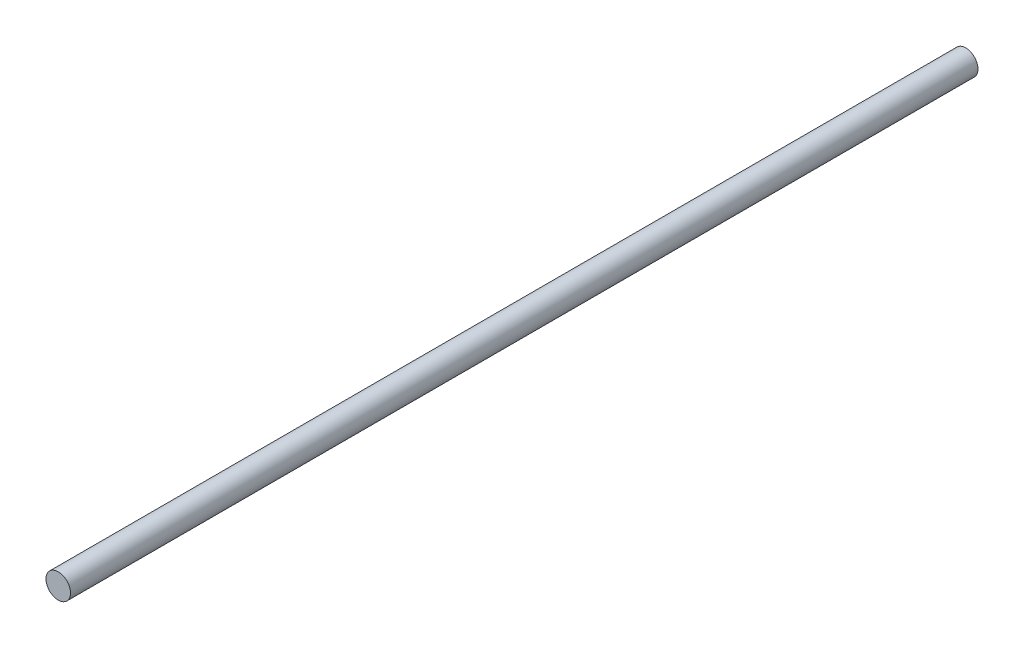
SolidWorks part; units mm, degrees
material "AISI 316 Stainless Steel Sheet (SS)"
ref_plane "Front (1)" through (0, 0, 0) normal (0, 0, 1) x (1, 0, 0)
ref_plane "Top (2)" through (0, 0, 0) normal (0, 1, 0) x (1, 0, 0)
ref_plane "Right (3)" through (0, 0, 0) normal (1, 0, 0) x (0, 0, -1)
ref_axis "X Axis" through (13.5064, 0, 0) along (-1, 0, 0)
ref_axis "Y Axis" through (0, 12.3593, 0) along (0, -1, 0)
ref_axis "Z Axis" through (0, 0, 14.1119) along (0, 0, -1)
sketch "Sketch2" plane through (0, 0, 0) normal (1, 0, 0) x (0, 0, -1)
  line L0 (-17.9, 0) -> (0, 0) construction
  line L1 (-17.9, 0) -> (277.9, 0)
  line L2 (-17.9, 0) -> (-17.9, 4)
  line L3 (-17.9, 4) -> (277.9, 4)
  line L4 (277.9, 0) -> (277.9, 4)
  dimension "D1" = 8
  dimension "D2" = 295.8
  dimension "D3" = 11.3
  dimension "D4" = 11.3
revolve "Revolve1" add sketch "Sketch2" angle 360 about L0
cosmetic thread "Cosmetic Thread2"
